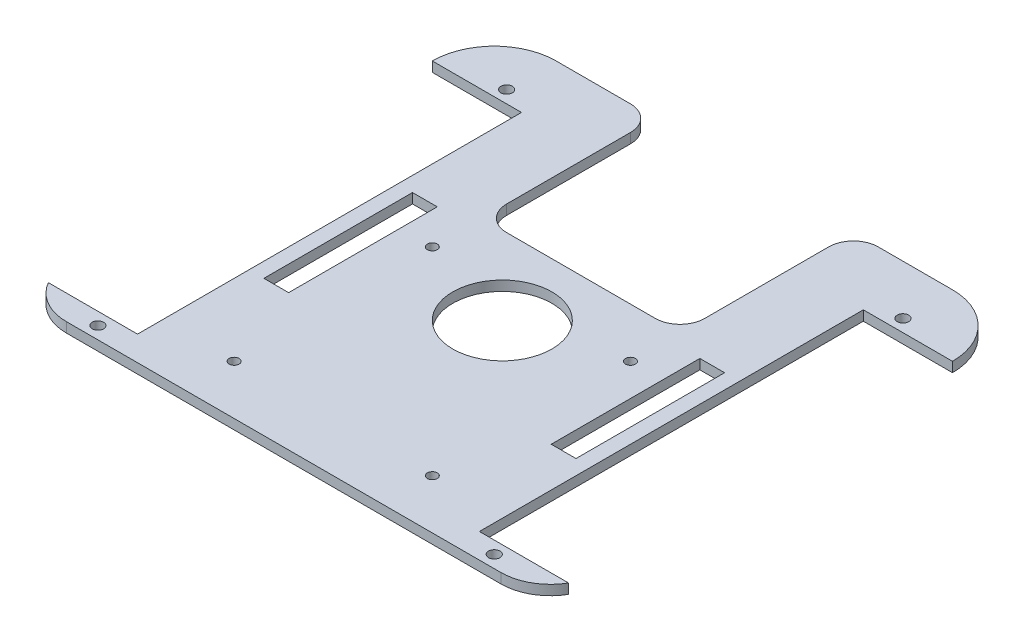
SolidWorks part; units mm, degrees
ref_plane "Front Plane" through (0, 0, 0) normal (0, 0, 1) x (1, 0, 0)
ref_plane "Top Plane" through (0, 0, 0) normal (0, 1, 0) x (1, 0, 0)
ref_plane "Right Plane" through (0, 0, 0) normal (1, 0, 0) x (0, 0, -1)
sketch "Sketch1" plane through (0, 0, 0) normal (0, 1, 0) x (1, 0, 0)
  line L0 (-145, 43.4935) -> (-109, 43.4935)
  line L2 (65, 68.4935) -> (65, 43.4935)
  line L3 (65, -121.5065) -> (-145, -121.5065)
  line L4 (-145, 68.4935) -> (-145, 43.4935)
  line L5 (-145, 68.4935) -> (-80, 68.4935)
  line L6 (-109, -34.0065) -> (-145, -34.0065) construction
  line L7 (-109, 43.4935) -> (-109, -111.5065)
  line L8 (-109, -111.5065) -> (-145, -111.5065)
  line L9 (-40, 71.907) -> (-40, -121.5065) construction
  line L10 (29, -111.5065) -> (65, -111.5065)
  line L11 (29, 43.4935) -> (29, -111.5065)
  line L12 (65, 43.4935) -> (29, 43.4935)
  line L13 (-145, -111.5065) -> (-145, -121.5065)
  line L14 (65, -111.5065) -> (65, -121.5065)
  line L15 (-80, 68.4935) -> (-80, -1.5065)
  line L16 (-80, -1.5065) -> (0, -1.5065)
  line L17 (0, -1.5065) -> (0, 68.4935)
  line L18 (0, 68.4935) -> (65, 68.4935)
  line L19 (23, -66.5065) -> (13, -66.5065)
  line L20 (-103, -6.5065) -> (-93, -6.5065)
  line L21 (-103, -6.5065) -> (-103, -66.5065)
  line L22 (-103, -66.5065) -> (-93, -66.5065)
  line L23 (-93, -6.5065) -> (-93, -66.5065)
  line L24 (-103, -6.5065) -> (-93, -66.5065) construction
  line L25 (-103, -66.5065) -> (-93, -6.5065) construction
  line L26 (13, -6.5065) -> (13, -66.5065)
  line L27 (23, -6.5065) -> (13, -6.5065)
  line L28 (23, -6.5065) -> (23, -66.5065)
  line L29 (-40, -61.5065) -> (29, -61.5065) construction
  circle A1 centre (-40.1479, -33.0929) radius 20
  circle A4 centre (-120, -116.5065) radius 2.32
  circle A5 centre (-120, 48.4935) radius 2.32
  circle A6 centre (40, 48.4935) radius 2.32
  circle A7 centre (40, -116.5065) radius 2.32
  circle A8 centre (-80, -101.5065) radius 2
  circle A9 centre (0, -101.5065) radius 2
  circle A10 centre (-80, -21.5065) radius 2
  circle A11 centre (0, -21.5065) radius 2
  point P0 (0, 0)
  point P2 (-98, -36.5065)
  point P20 (-145, -116.5065)
  dimension "D9" = 45
  dimension "D7" = 105
  dimension "D10" = 25
  dimension "D2" = 70
  dimension "D17" = 29
  dimension "D1" = 210
  dimension "D3" = 36
  dimension "D4" = 155
  dimension "D5" = 10
  dimension "D6" = 25
  dimension "D8" = 25
  dimension "D11" = 5
  dimension "D12" = 40
  dimension "D13" = 40
  dimension "D14" = 10
  dimension "D15" = 6
  dimension "D16" = 60
  dimension "D18" = 10
  dimension "D19" = 50
extrude "Boss-Extrude1" add sketch "Sketch1" along normal blind 4
fillet "Fillet2" radius 20 2 edges at (65, 2, 121.5065) (-145, 2, 121.5065)
fillet "Fillet3" radius 25 2 edges at (65, 2, -68.4935) (-145, 2, -68.4935)
fillet "Fillet4" radius 10 4 edges at (-80, 2, 1.5065) (0, 2, 1.5065) (0, 2, -68.4935) (-80, 2, -68.4935)
